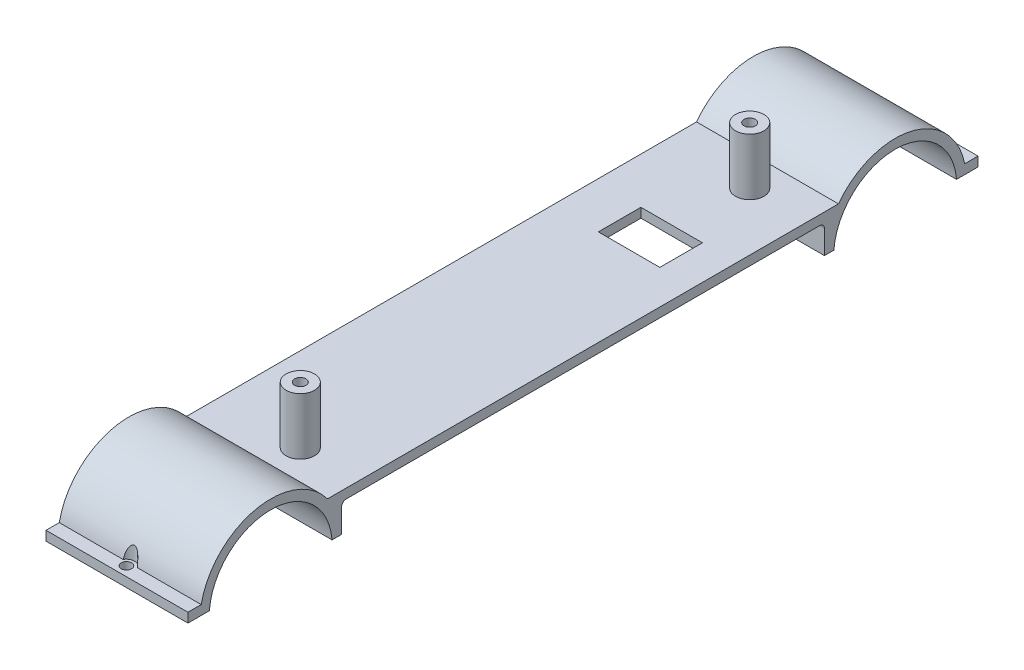
SolidWorks part; units mm, degrees
ref_plane "Спереди" through (0, 0, 0) normal (0, 0, 1) x (1, 0, 0)
ref_plane "Сверху" through (0, 0, 0) normal (0, 1, 0) x (1, 0, 0)
ref_plane "Справа" through (0, 0, 0) normal (1, 0, 0) x (0, 0, -1)
sketch "Эскиз1" plane through (0, 0, 0) normal (1, 0, 0) x (0, 0, -1)
  line L0 (-83.5, 0) -> (83.5, 0) construction
  line L1 (-83.5, 3) -> (-83.5, 1)
  line L2 (-83.5, 1) -> (-78.9615, 1)
  line L3 (-51.0385, 7) -> (-51.0385, 1)
  line L4 (78.9615, 1) -> (83.5, 1)
  line L5 (83.5, 1) -> (83.5, 3)
  line L6 (-83.5, 3) -> (-80.6969, 3)
  line L7 (-51.0385, 1) -> (-53.0385, 1)
  line L8 (80.6969, 3) -> (83.5, 3)
  line L9 (66, 13.2) -> (-66, 13) construction
  line L10 (-83.5, 1) -> (72.9784, 1) construction
  line L11 (-51.0385, 7) -> (51.0385, 7)
  line L12 (51.0385, 7) -> (51.0385, 1)
  line L13 (-54, 9) -> (54, 9)
  line L14 (51.0385, 1) -> (53.0385, 1)
  arc A0 (-78.9615, 1) -> (-53.0385, 1) centre (-66, 0) cw
  arc A1 (78.9615, 1) -> (53.0385, 1) centre (66, 0) ccw
  arc A2 (-80.6969, 3) -> (-54, 9) centre (-66, 0) cw
  arc A3 (80.6969, 3) -> (54, 9) centre (66, 0) ccw
  dimension "D5" = 1
  dimension "D6" = 1
  dimension "D9" = 2
  dimension "D10" = 2
  dimension "D13" = 2
  dimension "D14" = 13
  dimension "D15" = 13
  dimension "D2" = 15
  dimension "D16" = 15
  dimension "D1" = 167
  dimension "D3" = 17.5
  dimension "D4" = 17.5
  dimension "D7" = 2
  dimension "3" = 3
  dimension "D8" = 3
  dimension "D11" = 25.923
  dimension "D12" = 25.923
  dimension "D17" = 108
  dimension "D18" = 83.5
extrude "Бобышка-Вытянуть1" add sketch "Эскиз1" along normal blind 15 and the other way blind 15
fillet "Скругление4" radius 1 2 edges at (0, 7, -51.0385) (0, 7, 51.0385)
sketch "Эскиз2" plane through (0, 3, 0) normal (0, 1, 0) x (1, 0, 0)
  line L1 (-15, 83.5) -> (15, 83.5) construction
  circle A0 centre (0, 81.5) radius 1.1
  dimension "D2" = 2.2
  dimension "D1" = 2
extrude "Вырез-Вытянуть1" cut sketch "Эскиз2" against normal blind 10 and the other way blind 10
sketch "Эскиз3" plane through (0, 3, 0) normal (0, 1, 0) x (1, 0, 0)
  line L0 (-15, 80.6969) -> (-0.7517, 80.6969) construction
  line L1 (-15, 78.9615) -> (15, 78.9615) construction
  line L2 (-15, 83.5) -> (-15, 80.6969) construction
  circle A0 centre (0, 81.5) radius 1.7035
  point P9 (-15, 82.0985)
  dimension "D1" = 0.8031
  dimension "D2" = 2.5385
  dimension "D3" = 15
extrude "Вырез-Вытянуть2" cut sketch "Эскиз3" along normal blind 10
mirror "Зеркальное отражение1" about plane through (0, 0, 0) normal (0, 0, 1) of "Вырез-Вытянуть2", "Вырез-Вытянуть1"
sketch "Эскиз4" plane through (0, 9, 0) normal (0, 1, 0) x (1, 0, 0)
  line L0 (15, 54) -> (15, -54) construction
  circle A0 centre (2.75, 47.5) radius 3
  circle A1 centre (2.75, -47.5) radius 3
  dimension "D3" = 6
  dimension "D4" = 6
  dimension "D1" = 12.25
  dimension "D2" = 12.25
  dimension "D5" = 95
  dimension "D6" = 47.5
extrude "Бобышка-Вытянуть2" add sketch "Эскиз4" along normal blind 12
sketch "Эскиз5" plane through (0, 21, 0) normal (0, 1, 0) x (1, 0, 0)
  circle A0 centre (2.75, 47.5) radius 1.2
  circle A1 centre (2.75, -47.5) radius 1.2
  dimension "D1" = 2.4
  dimension "D2" = 2.4
extrude "Вырез-Вытянуть3" cut sketch "Эскиз5" against normal blind 8
sketch "Эскиз6" plane through (0, 9, 0) normal (0, 1, 0) x (1, 0, 0)
  line L1 (-5.25, 32.5) -> (7.75, 32.5)
  line L2 (-5.25, 32.5) -> (-5.25, 23.5)
  line L3 (-5.25, 23.5) -> (7.75, 23.5)
  line L4 (7.75, 32.5) -> (7.75, 23.5)
  point P4 (2.75, 47.5)
  dimension "D1" = 15
  dimension "D2" = 24
  dimension "D3" = 13
  dimension "D4" = 8
extrude "Вырез-Вытянуть4" cut sketch "Эскиз6" against normal blind 6
